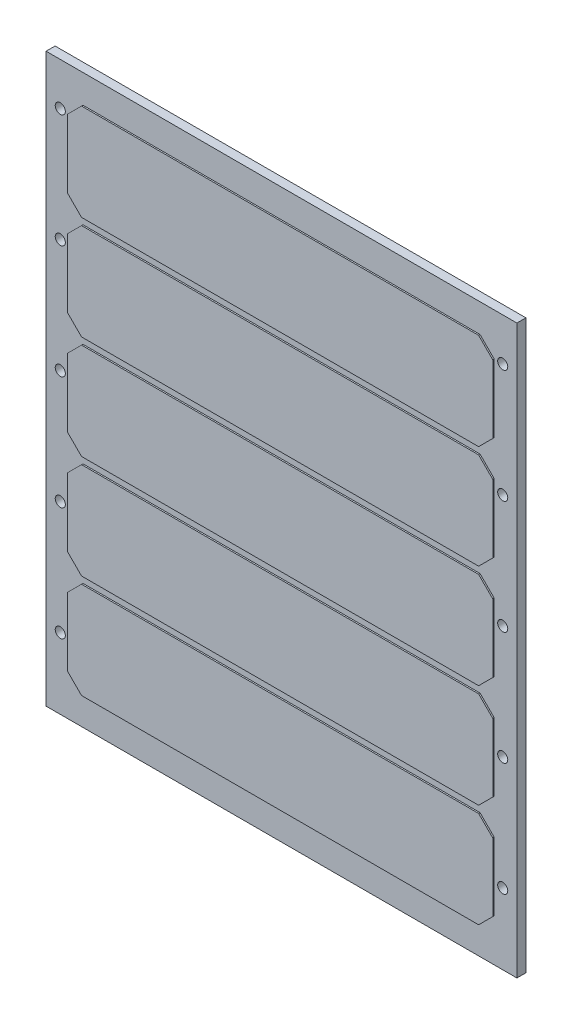
SolidWorks part; units mm, degrees
ref_plane "Front Plane" through (0, 0, 0) normal (0, 0, 1) x (1, 0, 0)
ref_plane "Top Plane" through (0, 0, 0) normal (0, 1, 0) x (1, 0, 0)
ref_plane "Right Plane" through (0, 0, 0) normal (1, 0, 0) x (0, 0, -1)
sketch "Sketch1" plane through (0, 0, 0) normal (0, 0, 1) x (1, 0, 0)
  line L1 (-41.5, -50) -> (41.5, -50)
  line L2 (-41.5, -50) -> (-41.5, 50)
  line L3 (-41.5, 50) -> (41.5, 50)
  line L4 (41.5, -50) -> (41.5, 50)
  line L5 (-41.5, -50) -> (41.5, 50) construction
  line L6 (-41.5, 50) -> (41.5, -50) construction
  point P0 (0, 0)
  dimension "D1" = 83
  dimension "D2" = 100
extrude "Boss-Extrude1" add sketch "Sketch1" along normal blind 1.5875
sketch "Sketch2" plane through (0, 0, 1.5875) normal (0, 0, 1) x (1, 0, 0)
  line L0 (-35, 45) -> (35, 45)
  line L1 (35, 45) -> (37.5, 42.5)
  line L2 (37.5, 42.5) -> (37.5, 30.5)
  line L3 (35, 28) -> (-35, 28)
  line L4 (-37.5, 30.5) -> (-37.5, 42.5)
  line L5 (-37.5, 42.5) -> (-35, 45)
  line L6 (0, 0) -> (0, 50) construction
  line L7 (41.5, 50) -> (-41.5, 50) construction
  line L8 (-35, 28) -> (-37.5, 30.5)
  line L9 (37.5, 30.5) -> (35, 28)
  line L10 (-35, 26.75) -> (35, 26.75)
  line L11 (35, 26.75) -> (37.5, 24.25)
  line L12 (37.5, 24.25) -> (37.5, 12.25)
  line L13 (35, 9.75) -> (-35, 9.75)
  line L14 (-37.5, 12.25) -> (-37.5, 24.25)
  line L15 (-37.5, 24.25) -> (-35, 26.75)
  line L16 (-35, 9.75) -> (-37.5, 12.25)
  line L17 (37.5, 12.25) -> (35, 9.75)
  line L18 (-35, 8.5) -> (35, 8.5)
  line L19 (35, 8.5) -> (37.5, 6)
  line L20 (37.5, 6) -> (37.5, -6)
  line L21 (35, -8.5) -> (-35, -8.5)
  line L22 (-37.5, -6) -> (-37.5, 6)
  line L23 (-37.5, 6) -> (-35, 8.5)
  line L24 (-35, -8.5) -> (-37.5, -6)
  line L25 (37.5, -6) -> (35, -8.5)
  line L26 (-35, -9.75) -> (35, -9.75)
  line L27 (35, -9.75) -> (37.5, -12.25)
  line L28 (37.5, -12.25) -> (37.5, -24.25)
  line L29 (35, -26.75) -> (-35, -26.75)
  line L30 (-37.5, -24.25) -> (-37.5, -12.25)
  line L31 (-37.5, -12.25) -> (-35, -9.75)
  line L32 (-35, -26.75) -> (-37.5, -24.25)
  line L33 (37.5, -24.25) -> (35, -26.75)
  line L34 (-35, -28) -> (35, -28)
  line L35 (35, -28) -> (37.5, -30.5)
  line L36 (37.5, -30.5) -> (37.5, -42.5)
  line L37 (35, -45) -> (-35, -45)
  line L38 (-37.5, -42.5) -> (-37.5, -30.5)
  line L39 (-37.5, -30.5) -> (-35, -28)
  line L40 (-35, -45) -> (-37.5, -42.5)
  line L41 (37.5, -42.5) -> (35, -45)
  line L42 (-41.5, -50) -> (41.5, -50) construction
  point P4 (37.5, 28)
  point P5 (-37.5, 28)
  point P20 (37.5, 9.75)
  point P21 (-37.5, 9.75)
  point P30 (37.5, -8.5)
  point P31 (-37.5, -8.5)
  point P40 (37.5, -26.75)
  point P41 (-37.5, -26.75)
  point P50 (37.5, -45)
  point P51 (-37.5, -45)
  dimension "D1" = 75
  dimension "D2" = 2.5
  dimension "D3" = 45
  dimension "D4" = 17
  dimension "D5" = 5
  dimension "D7" = 5
  dimension "D6" = 5
extrude "Boss-Extrude2" add sketch "Sketch2" along normal blind 0.25
hole_wizard "#0 Clearance Hole1" positions "Sketch4" profile "Sketch3" hole size "#0" standard "ANSI Inch"
sketch "Sketch4" plane through (0, 0, 1.5875) normal (0, 0, 1) x (1, 0, 0)
  line L0 (-41.5, 50) -> (-41.5, -50) construction
  line L1 (41.5, 50) -> (-41.5, 50) construction
  line L2 (-41.5, -50) -> (41.5, -50) construction
  line L3 (0, 50) -> (0, -50) construction
  point P56 (-39, 42.5)
  point P79 (-39, 22.5)
  point P80 (-39, 2.5)
  point P81 (-39, -17.5)
  point P82 (-39, -37.5)
  point P92 (39, -37.5)
  point P93 (39, -17.5)
  point P94 (39, 2.5)
  point P95 (39, 22.5)
  point P96 (39, 42.5)
  dimension "D1" = 2.5
  dimension "D2" = 7.5
  dimension "D3" = 5
  dimension "D4" = 20
sketch "Sketch3" plane through (-39, 42.5, 1.5875) normal (1, 0, 0) x (0, -1, 0)
  line L0 (0, 0) -> (0, 3.7092)
  line L1 (0, 3.7092) -> (0.889, 3.175)
  line L2 (0.889, 3.175) -> (0.889, 0)
  line L5 (0.889, 0) -> (0, 0)
  line L10 (0, 3.7092) -> (-0.889, 3.175) construction
  line L11 (0, -6.35) -> (0, 107.95) construction
  dimension "Hole Dia." = 1.778
  dimension "Hole Depth" = 3.175
  dimension "Drill Angle" = 118
